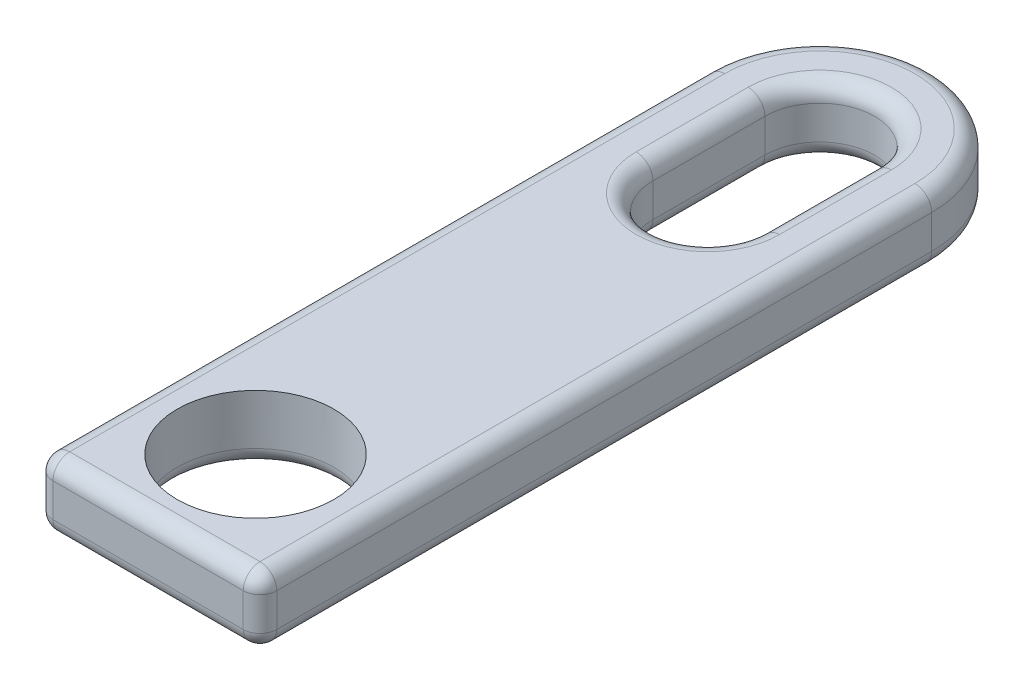
SolidWorks part; units mm, degrees
ref_plane "Front Plane" through (0, 0, 0) normal (0, 0, 1) x (1, 0, 0)
ref_plane "Top Plane" through (0, 0, 0) normal (0, 1, 0) x (1, 0, 0)
ref_plane "Right Plane" through (0, 0, 0) normal (1, 0, 0) x (0, 0, -1)
sketch "Sketch1" plane through (0, 0, 0) normal (0, 1, 0) x (1, 0, 0)
  line L0 (0, -7.4492) -> (0, -12.4492) construction
  line L6 (-5, -37.4492) -> (5, -37.4492)
  line L8 (2.45, -7.4492) -> (2.45, -12.4492)
  line L9 (-2.45, -7.4492) -> (-2.45, -12.4492)
  line L10 (-5, -7.4492) -> (5, -7.4492) construction
  line L11 (5, -7.4492) -> (5, -37.4492)
  line L12 (-5, -7.4492) -> (-5, -37.4492)
  line L13 (-5, -32.6492) -> (5, -32.6492) construction
  line L14 (0, -2.4492) -> (0, -37.4492) construction
  arc A4 (2.45, -7.4492) -> (-2.45, -7.4492) centre (0, -7.4492) ccw
  circle A5 centre (0, -32.6492) radius 3.5
  arc A6 (-2.45, -12.4492) -> (2.45, -12.4492) centre (0, -12.4492) ccw
  arc A7 (-5, -7.4492) -> (5, -7.4492) centre (0, -7.4492) cw
  point P3 (0, -9.9492)
  point P15 (0, -32.6492)
  point P17 (0, -7.4492)
  dimension "D5" = 4.8
  dimension "D2" = 2.45
  dimension "D7" = 7
  dimension "D1" = 5
  dimension "D4" = 30
  dimension "D9" = 10
extrude "Boss-Extrude1" add sketch "Sketch1" along normal blind 3
fillet "Fillet1" radius 0.75 19 edges at (0, 3, 37.4492) (2.45, 0, 9.9492) (0, 0, 14.8992) (-2.45, 0, 9.9492) (0, 0, 4.9992) (0, 0, 37.4492) (0, 3, 2.4492) (0, 0, 2.4492) (0, 3, 4.9992) (2.45, 3, 9.9492) (0, 3, 14.8992) (-2.45, 3, 9.9492) (0, 0, 36.1492) (-5, 3, 22.4492) (5, 3, 22.4492) (-5, 1.5, 37.4492) (5, 1.5, 37.4492) (-5, 0, 22.4492) (5, 0, 22.4492)
